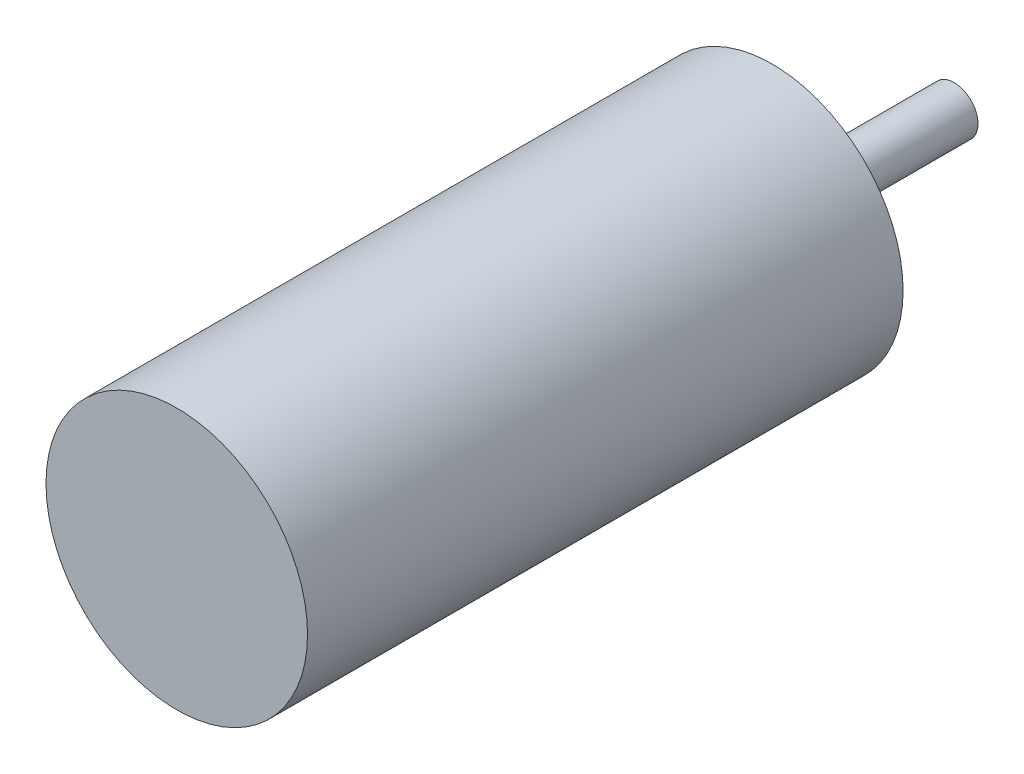
SolidWorks part; units mm, degrees
ref_plane "Front Plane" through (0, 0, 0) normal (0, 0, 1) x (1, 0, 0)
ref_plane "Top Plane" through (0, 0, 0) normal (0, 1, 0) x (1, 0, 0)
ref_plane "Right Plane" through (0, 0, 0) normal (1, 0, 0) x (0, 0, -1)
sketch "Sketch1" plane through (0, 0, 0) normal (0, 0, 1) x (1, 0, 0)
  circle A0 centre (0, 0) radius 11
  circle A1 centre (0, 0) radius 2
  dimension "D1" = 22
  dimension "D2" = 4
extrude "Boss-Extrude4" add sketch "Sketch1" along normal blind 50.1 contours A1 | A0 A1 region at (-10.6889, 0, 0) region at (0, 0, 0)
extrude "Boss-Extrude5" add sketch "Sketch1<6>" against normal blind 15.3 contours A1 region at (0, 0, 0)
sketch "Sketch1<6>" plane through (0, 0, 0) normal (0, 0, 1) x (1, 0, 0) same geometry as "Sketch1"
